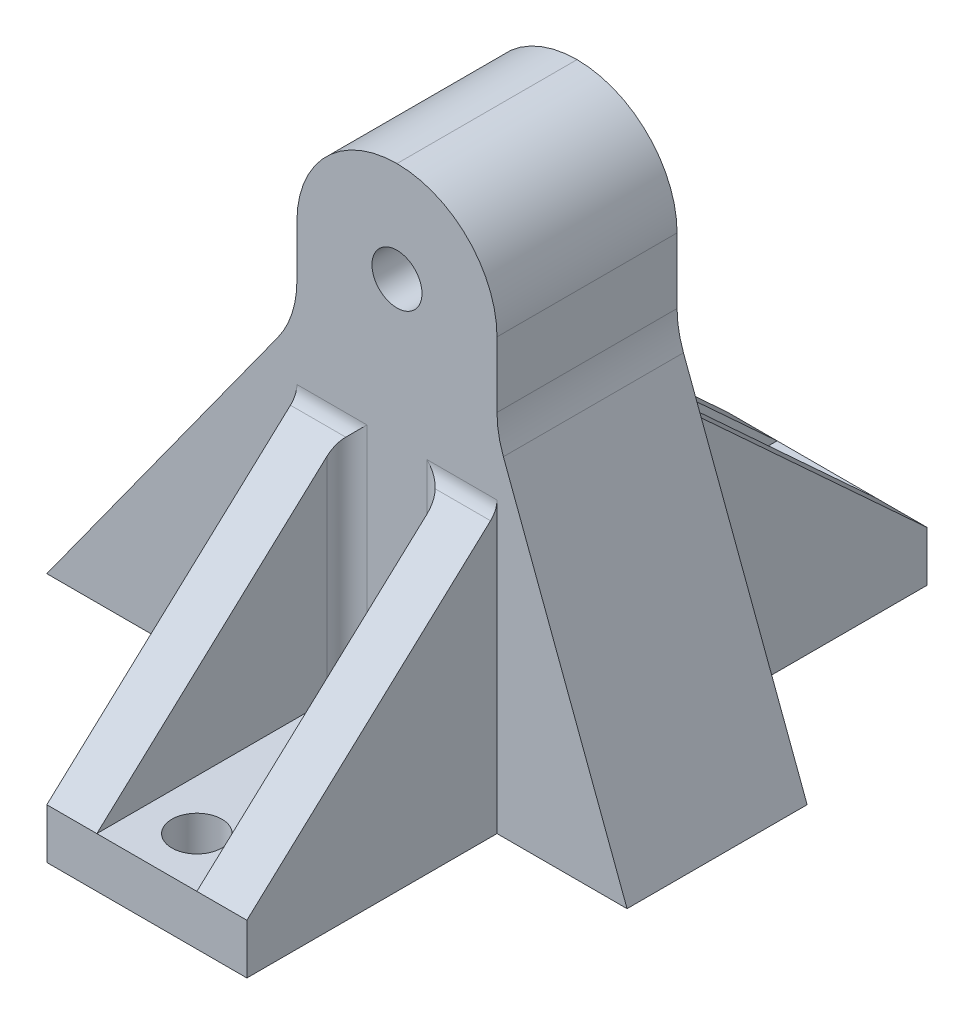
SolidWorks part; units mm, degrees
ref_plane "Front Plane" through (0, 0, 0) normal (0, 0, 1) x (1, 0, 0)
ref_plane "Top Plane" through (0, 0, 0) normal (0, 1, 0) x (1, 0, 0)
ref_plane "Right Plane" through (0, 0, 0) normal (1, 0, 0) x (0, 0, -1)
sketch "Sketch1" plane through (0, 0, 0) normal (0, 0, 1) x (1, 0, 0)
  line L1 (-10, 40) -> (10, 40)
  line L2 (-10, 40) -> (-10, -13)
  line L4 (10, 40) -> (10, -13)
  line L10 (-10, -13) -> (10, -13)
  circle A0 centre (0, 30) radius 2.5
  point P0 (0, 0)
  dimension "D1" = 5
  dimension "D6" = 10
  dimension "D7" = 10
  dimension "D2" = 20
  dimension "D3" = 13
  dimension "D4" = 40
  dimension "D5" = 10
extrude "Boss-Extrude1" add sketch "Sketch1" along normal blind 18
fillet "Fillet1" radius 10 2 edges at (-10, 40, 9) (10, 40, 9)
sketch "Sketch2" plane through (0, 0, 0) normal (0, 0, 1) x (1, 0, 0)
  line L0 (-10, 21.641) -> (-35, -13)
  line L1 (-10, 21.641) -> (-10, -13)
  line L2 (-35, -13) -> (-10, -13)
  line L3 (10, 21.641) -> (10, -13)
  line L4 (10, -13) -> (10, 30) construction
  line L5 (10, -13) -> (23, -13)
  line L6 (23, -13) -> (10, 21.641)
  line L8 (-10, 21.641) -> (10, 21.641) construction
  dimension "D1" = 25
  dimension "D2" = 13
  dimension "D3" = 21.641
extrude "Boss-Extrude2" add sketch "Sketch2" along normal blind 18
sketch "Sketch3" plane through (0, 0, 0) normal (0, 0, 1) x (1, 0, 0)
  line L0 (-35, -13) -> (23, -13) construction
  line L1 (-10, -13) -> (10, -13)
  line L2 (-10, -13) -> (-10, -8)
  line L3 (-10, -8) -> (10, -8)
  line L4 (10, -13) -> (10, -8)
  dimension "D1" = 20
  dimension "D2" = 10
  dimension "D3" = 5
extrude "Boss-Extrude3" add sketch "Sketch3" along normal blind 43 and the other way blind 25
sketch "Sketch6" plane through (-10, 0, 0) normal (-1, 0, 0) x (0, 0, 1)
  line L0 (-25, -8) -> (0, 15)
  line L1 (0, 21.641) -> (0, -13) construction
  point P4 (0, 21.641)
  point P5 (0, 16.27)
  dimension "D1" = 15
rib "Rib8" sketch "Sketch6" sketch "Sketch6" thickness 5 extrusion direction parallel to sketch draft on no parameters "D1"=5
sketch "Sketch7" plane through (-10, 0, 0) normal (-1, 0, 0) x (0, 0, 1)
  line L0 (18, 15) -> (43, -8)
  line L1 (18, 21.641) -> (18, -13) construction
  point P4 (0, 0)
  point P6 (18, 15)
  dimension "D1" = 15
rib "Rib9" sketch "Sketch7" sketch "Sketch7" thickness 5 extrusion direction parallel to sketch draft on no parameters "D1"=5
mirror "Mirror1" about plane through (0, 0, 0) normal (1, 0, 0) of "Rib8", "Rib9"
sketch "Sketch8" plane through (0, 0, 0) normal (0, 1, 0) x (1, 0, 0)
  line L0 (0, 20) -> (0, 0) construction
  line L1 (5, 25) -> (-5, 25) construction
  line L2 (5, -43) -> (-5, -43) construction
  line L3 (0, 0) -> (0, -38) construction
  circle A0 centre (0, 20) radius 2.5
  circle A1 centre (0, -38) radius 2.5
  circle A2 centre (-22.5, -9) radius 7.5
  point P13 (0, 0)
  dimension "D1" = 5
  dimension "D2" = 5
  dimension "D4" = 5
  dimension "D3" = 5
  dimension "D5" = 15
  dimension "D6" = 22.5
  dimension "D7" = 9
extrude "Cut-Extrude1" cut sketch "Sketch8" against normal through all both and the other way through all
fillet "Fillet3" radius 10 2 edges at (10, 21.641, 9) (-10, 21.641, 9)
fillet "Fillet4" radius 2 10 edges at (7.5, 15, 18) (-7.5, 15, 18) (7.5, 15, 0) (-7.5, 15, 0) (-5, 3.5, 0) (0, -8, 0) (5, 3.5, 0) (5, 3.5, 18) (0, -8, 18) (-5, 3.5, 18)
